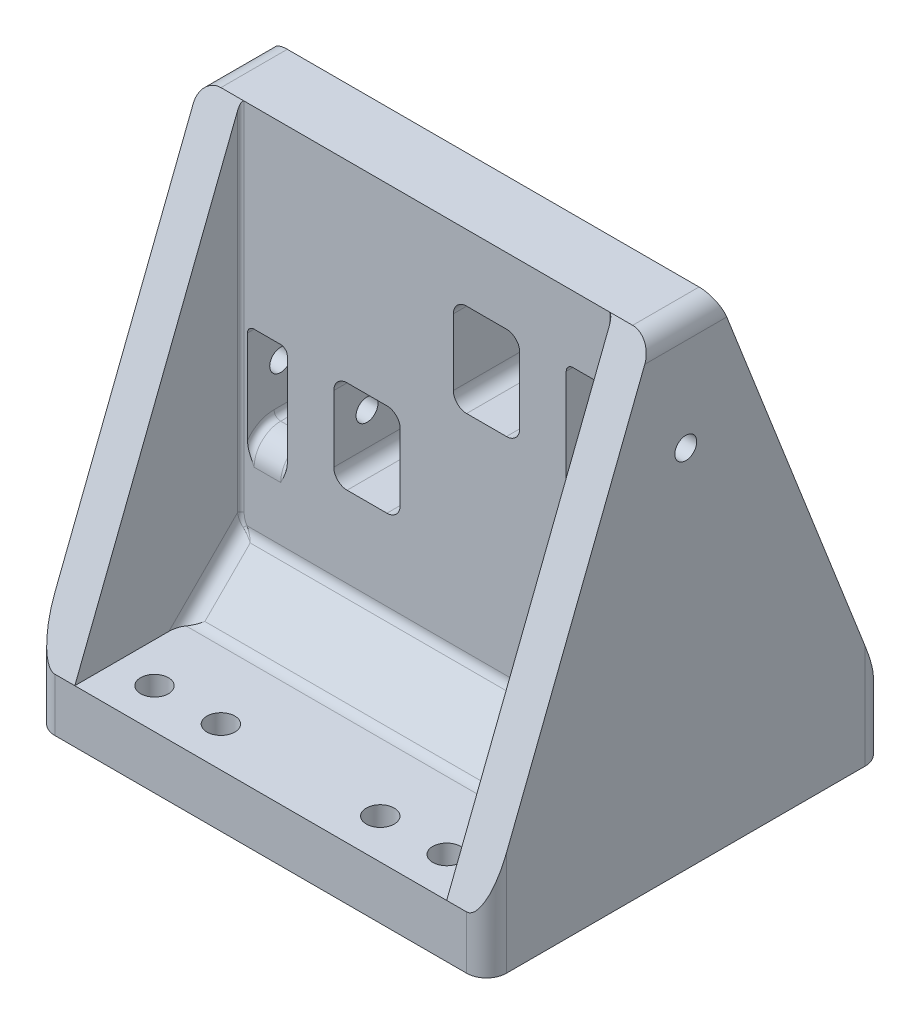
SolidWorks part; units mm, degrees
material "ABS"
ref_plane "前视基准面" through (0, 0, 0) normal (0, 0, 1) x (1, 0, 0)
ref_plane "上视基准面" through (0, 0, 0) normal (0, 1, 0) x (1, 0, 0)
ref_plane "右视基准面" through (0, 0, 0) normal (1, 0, 0) x (0, 0, -1)
other "Configuration Table"
sketch "草图1" plane through (0, 0, 0) normal (0, 1, 0) x (1, 0, 0)
  line L1 (0, 0) -> (68, 0)
  line L2 (0, 0) -> (0, 60)
  line L3 (0, 60) -> (68, 60)
  line L4 (68, 0) -> (68, 60)
  dimension "D1" = 60
  dimension "D2" = 68
extrude "凸台-拉伸1" add sketch "草图1" along normal blind 8
ref_plane "基准面1" through (0, 0, -30) normal (0, 0, 1) x (1, 0, 0)
sketch "草图2" plane through (0, 0, -30) normal (0, 0, 1) x (1, 0, 0)
  line L0 (0, 0) -> (68, 0) construction
  line L1 (7, 43) -> (13, 43)
  line L2 (7, 43) -> (7, 29)
  line L3 (7, 29) -> (13, 29)
  line L4 (13, 43) -> (13, 29)
  line L5 (7, 43) -> (13, 29) construction
  line L6 (7, 29) -> (13, 43) construction
  line L7 (55, 62) -> (61, 62)
  line L8 (55, 62) -> (55, 48)
  line L9 (55, 48) -> (61, 48)
  line L10 (61, 62) -> (61, 48)
  line L11 (55, 62) -> (61, 48) construction
  line L12 (55, 48) -> (61, 62) construction
  line L13 (0, 8) -> (0, 0) construction
  line L14 (68, 8) -> (68, 0) construction
  line L15 (0, 8) -> (0, 72)
  line L17 (0, 72) -> (68, 72)
  line L18 (0, 8) -> (68, 8)
  line L19 (0, 8) -> (68, 8) construction
  line L20 (68, 8) -> (68, 72)
  point P0 (10, 36)
  point P5 (58, 55)
  dimension "D1" = 36
  dimension "D2" = 55
  dimension "D3" = 10
  dimension "D4" = 10
  dimension "D5" = 6
  dimension "D6" = 14
  dimension "D7" = 14
  dimension "D8" = 6
  dimension "D10" = 10
extrude "凸台-拉伸2" add sketch "草图2" along normal mid plane 10
sketch "草图5" plane through (0, 0, -25) normal (0, 0, 1) x (1, 0, 0)
  line L0 (13, 36) -> (25, 36) construction
  line L1 (13, 29) -> (13, 43) construction
  line L2 (55, 55) -> (43, 55) construction
  line L3 (20, 29) -> (30, 29)
  line L4 (20, 29) -> (20, 43)
  line L5 (20, 43) -> (30, 43)
  line L6 (30, 29) -> (30, 43)
  line L7 (20, 29) -> (30, 43) construction
  line L8 (20, 43) -> (30, 29) construction
  line L9 (55, 62) -> (55, 48) construction
  line L10 (0, 72) -> (0, 8) construction
  line L11 (48, 48) -> (38, 48)
  line L12 (48, 48) -> (48, 62)
  line L13 (48, 62) -> (38, 62)
  line L14 (38, 48) -> (38, 62)
  line L15 (48, 48) -> (38, 62) construction
  line L16 (48, 62) -> (38, 48) construction
  line L17 (68, 8) -> (68, 72) construction
  dimension "D1" = 10
  dimension "D2" = 10
  dimension "D3" = 14
  dimension "D4" = 20
  dimension "D5" = 14
  dimension "D6" = 20
extrude "切除-拉伸3" cut sketch "草图5" against normal through all
sketch "草图3" plane through (0, 0, 0) normal (-1, 0, 0) x (0, 0, 1)
  line L0 (-30, -4.4) -> (-30, 4.4) construction
  line L1 (-30, 36) -> (-30, 72) construction
  line L3 (-25, 72) -> (-35, 72) construction
  circle A0 centre (-30, 36) radius 1.65
  dimension "D1" = 3.3
  dimension "D2" = 7
extrude "切除-拉伸1" cut sketch "草图3" against normal up to surface (20 mm away) up to face at (20, 36, -30)
sketch "草图4" plane through (68, 0, 0) normal (1, 0, 0) x (0, 0, -1)
  line L0 (30, 72) -> (30, 55) construction
  line L1 (25, 72) -> (35, 72) construction
  circle A0 centre (30, 55) radius 1.65
  dimension "D1" = 3.3
  dimension "D2" = 7
extrude "切除-拉伸2" cut sketch "草图4" against normal up to surface (20 mm away) up to face at (48, 55, -30)
sketch "草图6" plane through (0, 0, 0) normal (-1, 0, 0) x (0, 0, 1)
  line L0 (-35, 72) -> (-60, 8)
  line L1 (-60, 8) -> (-35, 8)
  line L2 (-60, 8) -> (-35, 8) construction
  line L3 (-35, 8) -> (-35, 72)
  line L4 (-25, 72) -> (-25, 8)
  line L5 (-25, 8) -> (0, 8)
  line L6 (0, 8) -> (-25, 72)
extrude "凸台-拉伸3" add sketch "草图6" against normal blind 6
ref_plane "基准面2" through (34, 0, 0) normal (1, 0, 0) x (0, 0, -1)
mirror "镜向1" about plane through (34, 0, 0) normal (1, 0, 0) of "凸台-拉伸3"
sketch "草图7" plane through (0, 8, 0) normal (0, 1, 0) x (1, 0, 0)
  line L0 (34, 60) -> (34, 0) construction
  line L1 (62, 60) -> (6, 60) construction
  line L2 (6, 0) -> (62, 0) construction
  line L3 (0, 30) -> (68, 30) construction
  line L4 (0, 25) -> (0, 35) construction
  line L5 (68, 25) -> (68, 35) construction
  line L6 (6, 0) -> (6, 25) construction
  circle A0 centre (12, 6) radius 2.1
  circle A1 centre (56, 6) radius 2.1
  circle A2 centre (56, 54) radius 2.1
  circle A3 centre (12, 54) radius 2.1
  circle A4 centre (22, 6) radius 2.1
  circle A5 centre (46, 6) radius 2.1
  circle A6 centre (46, 54) radius 2.1
  circle A7 centre (22, 54) radius 2.1
  dimension "D1" = 4.2
  dimension "D2" = 6
  dimension "D3" = 6
  dimension "D4" = 2
extrude "切除-拉伸4" cut sketch "草图7" against normal through all
fillet "圆角2" radius 4 4 edges at (58, 62, -35) (10, 43, -35) (10, 29, -25) (58, 48, -25)
fillet "圆角1" radius 1 16 edges at (55, 62, -28) (55, 48, -32) (61, 62, -28) (7, 43, -28) (7, 29, -32) (13, 29, -32) (13, 43, -28) (61, 48, -32) (55, 63.1716, -33.8284) (55, 46.8284, -26.1716) (61, 63.1716, -33.8284) (7, 44.1716, -33.8284) (7, 27.8284, -26.1716) (13, 27.8284, -26.1716) (13, 44.1716, -33.8284) (61, 46.8284, -26.1716)
fillet "圆角3" radius 2 8 edges at (48, 62, -30) (48, 48, -30) (38, 48, -30) (38, 62, -30) (20, 43, -30) (30, 43, -30) (30, 29, -30) (20, 29, -30)
fillet "圆角4" radius 3 4 edges at (68, 4, 0) (68, 4, -60) (0, 4, -60) (0, 4, 0)
chamfer "倒角1" distance 8 angle 45 2 edges at (34, 8, -35) (34, 8, -25)
fillet "圆角5" radius 2 8 edges at (34, 16, -25) (62, 12, -21) (34, 8, -17) (6, 12, -21) (34, 8, -43) (62, 12, -39) (34, 16, -35) (6, 12, -39)
fillet "圆角6" radius 3 2 edges at (0, 72, -30) (68, 72, -30)
fillet "圆角7" radius 0.5 12 edges at (7.2346, 16.0631, -24.8478) (6.1522, 17.746, -25) (60.7654, 16.0631, -24.8478) (61.8478, 17.746, -25) (60.7654, 16.0631, -35.1522) (61.8478, 17.746, -35) (7.2346, 16.0631, -35.1522) (6.1522, 17.746, -35) (6, 45.4142, -25) (62, 45.4142, -25) (62, 45.4142, -35) (6, 45.4142, -35)
